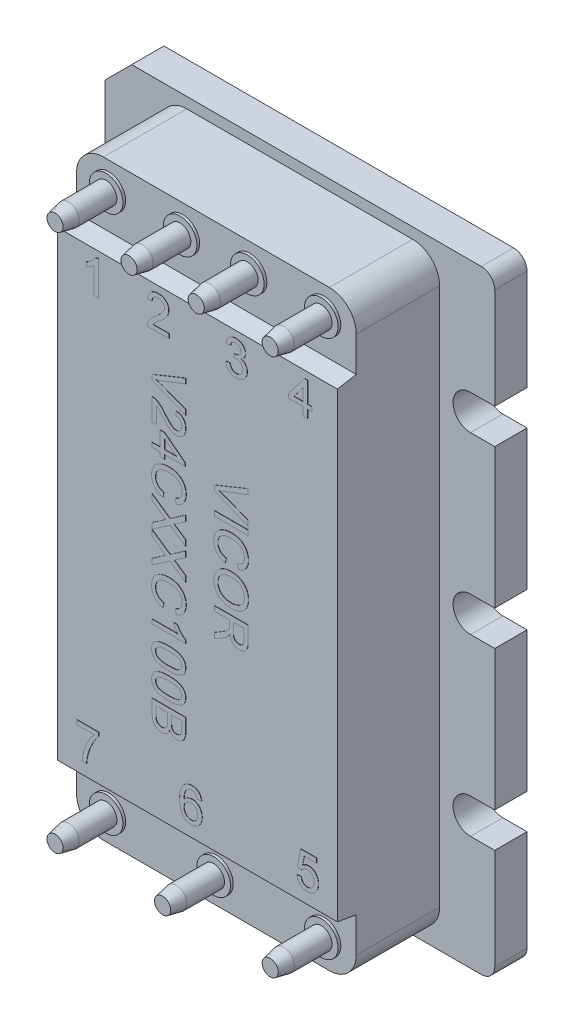
SolidWorks part; units mm, degrees
material "6061 Alloy"
ref_plane "Plane1" through (0, 0, 0) normal (0, 0, 1) x (1, 0, 0)
ref_plane "Plane2" through (0, 0, 0) normal (0, 1, 0) x (1, 0, 0)
ref_plane "Plane3" through (0, 0, 0) normal (1, 0, 0) x (0, 0, -1)
sketch "Sketch1" plane through (0, 0, 0) normal (0, 0, 1) x (1, 0, 0)
  line L0 (-18.415, -28.956) -> (18.415, 28.956) construction
  line L1 (-17.145, -28.956) -> (17.145, -28.956)
  line L2 (-18.415, -27.686) -> (-18.415, 26.416)
  line L3 (-15.875, 28.956) -> (17.145, 28.956)
  line L4 (18.415, -27.686) -> (18.415, 27.686)
  line L5 (-18.415, 26.416) -> (-15.875, 28.956)
  arc A0 (17.145, 28.956) -> (18.415, 27.686) centre (17.145, 27.686) cw
  arc A1 (17.145, -28.956) -> (18.415, -27.686) centre (17.145, -27.686) ccw
  arc A2 (-17.145, -28.956) -> (-18.415, -27.686) centre (-17.145, -27.686) cw
  point P2 (-18.415, 28.956)
  dimension "D5" = 1.27
  dimension "D1" = 36.83
  dimension "D2" = 57.912
  dimension "D3" = 2.54
  dimension "D4" = 45
extrude "Extrude1" add sketch "Sketch1" along normal blind 3.048
sketch "Sketch2" plane through (0, 0, 3.048) normal (0, 0, 1) x (1, 0, 0)
  line L0 (0, 0) -> (16.129, 0) construction
  line L1 (18.415, -27.686) -> (18.415, 27.686) construction
  line L2 (18.415, 1.651) -> (16.129, 1.651)
  line L3 (18.415, 1.651) -> (18.415, -1.651)
  line L4 (18.415, -1.651) -> (16.129, -1.651)
  line L5 (16.129, 1.651) -> (16.129, -1.651) construction
  line L6 (18.415, 16.51) -> (15.0865, 16.51) construction
  line L7 (18.415, -14.859) -> (16.129, -14.859)
  line L8 (18.415, 18.161) -> (16.129, 18.161)
  line L9 (18.415, 18.161) -> (18.415, 14.859)
  line L10 (18.415, 14.859) -> (16.129, 14.859)
  line L11 (16.129, 18.161) -> (16.129, 14.859) construction
  line L12 (18.415, -18.161) -> (18.415, -14.859)
  line L13 (18.415, -18.161) -> (16.129, -18.161)
  line L14 (0, 0) -> (0, -7.2577) construction
  line L15 (-18.415, -18.161) -> (-16.129, -18.161)
  line L16 (-18.415, -18.161) -> (-18.415, -14.859)
  line L17 (-18.415, 14.859) -> (-16.129, 14.859)
  line L18 (-18.415, 18.161) -> (-18.415, 14.859)
  line L19 (-18.415, 18.161) -> (-16.129, 18.161)
  line L20 (-18.415, -14.859) -> (-16.129, -14.859)
  line L21 (-18.415, -1.651) -> (-16.129, -1.651)
  line L22 (-18.415, 1.651) -> (-18.415, -1.651)
  line L23 (-18.415, 1.651) -> (-16.129, 1.651)
  arc A0 (16.129, 1.651) -> (16.129, -1.651) centre (16.129, 0) ccw
  arc A1 (16.129, 18.161) -> (16.129, 14.859) centre (16.129, 16.51) ccw
  arc A2 (16.129, -18.161) -> (16.129, -14.859) centre (16.129, -16.51) cw
  arc A3 (-16.129, -18.161) -> (-16.129, -14.859) centre (-16.129, -16.51) ccw
  arc A4 (-16.129, 18.161) -> (-16.129, 14.859) centre (-16.129, 16.51) cw
  arc A5 (-16.129, 1.651) -> (-16.129, -1.651) centre (-16.129, 0) cw
  dimension "D1" = 3.302
  dimension "D2" = 2.286
  dimension "D3" = 3.302
  dimension "D4" = 16.51
  dimension "D5" = 32.258
extrude "Cut-Extrude1" cut sketch "Sketch2" against normal through all
sketch "Sketch3" plane through (0, 0, 3.048) normal (0, 0, 1) x (1, 0, 0)
  line L0 (-13.208, -27.94) -> (13.208, 27.94) construction
  line L1 (-10.668, 27.94) -> (10.668, 27.94)
  line L2 (-13.208, 25.4) -> (-13.208, -25.4)
  line L3 (-10.668, -27.94) -> (10.668, -27.94)
  line L4 (13.208, 25.4) -> (13.208, -25.4)
  arc A0 (-10.668, 27.94) -> (-13.208, 25.4) centre (-10.668, 25.4) ccw
  arc A1 (10.668, 27.94) -> (13.208, 25.4) centre (10.668, 25.4) cw
  arc A2 (10.668, -27.94) -> (13.208, -25.4) centre (10.668, -25.4) ccw
  arc A3 (-13.208, -25.4) -> (-10.668, -27.94) centre (-10.668, -25.4) ccw
  dimension "D3" = 2.54
  dimension "D1" = 26.416
  dimension "D2" = 55.88
extrude "Extrude2" add sketch "Sketch3" along normal blind 9.652
sketch "Sketch4" plane through (0, 0, 12.7) normal (0, 0, 1) x (1, 0, 0)
  line L0 (0, 0) -> (33.0065, 0) construction
  line L1 (-29.9882, 34.8527) -> (31.546, 34.8527)
  line L2 (-29.9882, 34.8527) -> (-29.9882, 22.098)
  line L3 (-29.9882, 22.098) -> (31.546, 22.098)
  line L4 (31.546, 34.8527) -> (31.546, 22.098)
  line L5 (17.145, 28.956) -> (-15.875, 28.956) construction
  line L6 (31.546, -34.8527) -> (31.546, -22.098)
  line L7 (-29.9882, -22.098) -> (31.546, -22.098)
  line L8 (-29.9882, -34.8527) -> (-29.9882, -22.098)
  line L9 (-29.9882, -34.8527) -> (31.546, -34.8527)
  dimension "D1" = 6.858
extrude "Cut-Extrude2" cut sketch "Sketch4" against normal offset from surface (1.778 mm away) 10.922 up to face at (0.0479, -0.0479, 0)
draft "Draft1" type of draft neutral plane draft angle 10 faces to draft 2 face at (0, -22.098, 11.811) face at (0, 22.098, 11.811) neutral plane through (17.145, 27.686, 10.922) neutral plane normal (0, 0, 1) parameters "D1"=10
sketch "Sketch5" plane through (0, 0, 10.922) normal (0, 0, 1) x (1, 0, 0)
  line L0 (-10.16, 25.4) -> (-3.175, 25.4) construction
  line L1 (-3.175, 25.4) -> (3.175, 25.4) construction
  line L2 (3.175, 25.4) -> (10.16, 25.4) construction
  line L3 (-10.16, -25.4) -> (10.16, -25.4) construction
  line L4 (0, 0) -> (11.0995, 0) construction
  line L5 (-18.415, 26.416) -> (-18.415, 18.161) construction
  circle A0 centre (-10.16, 25.4) radius 1.5875
  circle A1 centre (-3.175, 25.4) radius 1.5875
  circle A2 centre (3.175, 25.4) radius 1.5875
  circle A3 centre (10.16, 25.4) radius 1.5875
  circle A4 centre (0, -25.4) radius 1.5875
  circle A8 centre (10.16, -25.4) radius 1.5875
  circle A10 centre (-10.16, -25.4) radius 1.5875
  dimension "D1" = 3.175
  dimension "D2" = 8.255
  dimension "D4" = 6.985
  dimension "D5" = 13.335
  dimension "D6" = 20.32
  dimension "D7" = 10.16
  dimension "D3" = 25.4
extrude "Extrude3" add sketch "Sketch5" along normal blind 0.254
sketch "Sketch6" plane through (0, 0, 11.176) normal (0, 0, 1) x (1, 0, 0)
  circle A0 centre (-10.16, 25.4) radius 1.016
  circle A1 centre (-3.175, 25.4) radius 1.016
  circle A2 centre (10.16, 25.4) radius 1.016
  circle A3 centre (0, -25.4) radius 1.016
  circle A4 centre (-10.16, -25.4) radius 1.016
  circle A5 centre (3.175, 25.4) radius 1.016
  circle A7 centre (10.16, -25.4) radius 1.016
  dimension "D1" = 2.032
extrude "Extrude4" add sketch "Sketch6" along normal blind 4.826
chamfer "Chamfer1" distance 1.27 distance2 0.254 7 edges at (11.176, -25.4, 16.002) (1.016, -25.4, 16.002) (-9.144, -25.4, 16.002) (11.176, 25.4, 16.002) (4.191, 25.4, 16.002) (-2.159, 25.4, 16.002) (-9.144, 25.4, 16.002) first distance on face at (11.176, -25.4, 16.002) first distance on face at (1.016, -25.4, 16.002) first distance on face at (-9.144, -25.4, 16.002) first distance on face at (11.176, 25.4, 16.002) first distance on face at (4.191, 25.4, 16.002) first distance on face at (-2.159, 25.4, 16.002) first distance on face at (-9.144, 25.4, 16.002)
sketch "Sketch8" plane through (0, 0, 12.7) normal (0, 0, 1) x (1, 0, 0)
  text T0 "1   2    3   4"
extrude "Extrude6" add sketch "Sketch8" along normal blind 0.0254
sketch "Sketch9" plane through (0, 0, 12.7) normal (0, 0, 1) x (1, 0, 0)
  text T0 "7      6       5"
extrude "Extrude7" add sketch "Sketch9" along normal blind 0.0254
sketch "Sketch7" plane through (5.4941, 12.2354, 12.7) normal (0, 0, 1) x (0, -1, 0)
  text T0 "     VICOR\r\nV24CXXC100B"
extrude "Extrude5" add sketch "Sketch7" along normal blind 0.0254
sketch "Sketch10" plane through (0, 0, 0) normal (0, 0, -1) x (-1, 0, 0)
  text T0 "     VICOR\r\nV24CXXC100B"
extrude "Extrude8" add sketch "Sketch10" along normal blind 0.0254
